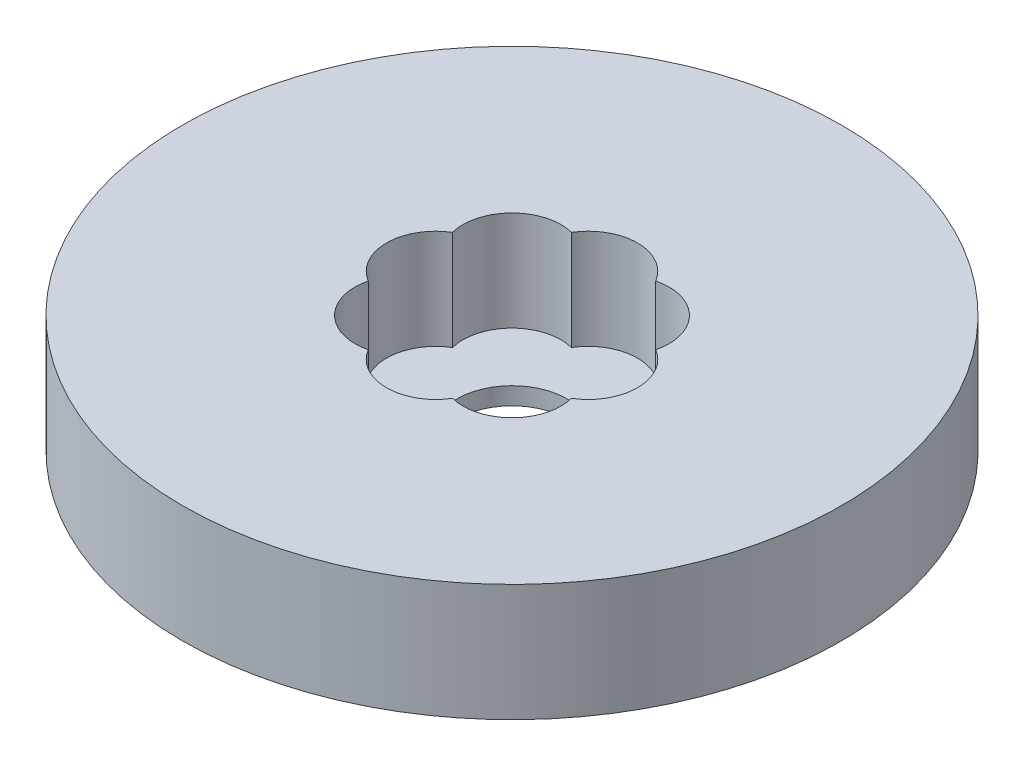
SolidWorks part; units mm, degrees
ref_plane "Front Plane" through (0, 0, 0) normal (0, 0, 1) x (1, 0, 0)
ref_plane "Top Plane" through (0, 0, 0) normal (0, 1, 0) x (1, 0, 0)
ref_plane "Right Plane" through (0, 0, 0) normal (1, 0, 0) x (0, 0, -1)
sketch "Sketch1" plane through (0, 0, 0) normal (0, 1, 0) x (1, 0, 0)
  circle A0 centre (0, 0) radius 45
  dimension "FLANGE_OD" = 90
extrude "Boss-Extrude1" add sketch "Sketch1" along normal blind 16
sketch "Sketch2" plane through (0, 0, 0) normal (0, 1, 0) x (1, 0, 0)
  circle A0 centre (0, 0) radius 7.5
  dimension "BORE_D" = 15
extrude "Cut-Extrude1" cut sketch "Sketch2" along normal through all
sketch "Sketch3" plane through (0, 16, 0) normal (0, 1, 0) x (1, 0, 0)
  circle A0 centre (0, 0) radius 10.4309 construction
  circle A1 centre (-10.4309, 0) radius 6.7
  dimension "BOLT_D" = 13.4
  dimension "BOLT_PCD" = 20.8619
extrude "Cut-Extrude2" cut sketch "Sketch3" against normal blind 13.6178
pattern_circular "CirPattern1" count 8 over 360 about axis through (0, 0, 0) along (0, 1, 0) of "Cut-Extrude2"
